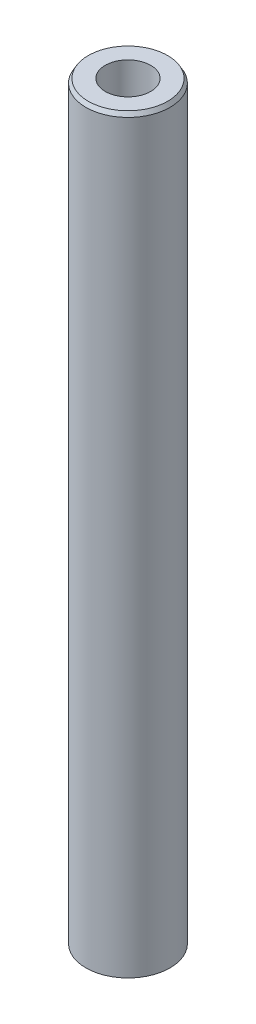
SolidWorks part; units mm, degrees
ref_plane "Front Plane" through (0, 0, 0) normal (0, 0, 1) x (1, 0, 0)
ref_plane "Top Plane" through (0, 0, 0) normal (0, 1, 0) x (1, 0, 0)
ref_plane "Right Plane" through (0, 0, 0) normal (1, 0, 0) x (0, 0, -1)
sketch "Sketch1" plane through (0, 0, 0) normal (0, 1, 0) x (1, 0, 0)
  circle A0 centre (0, 0) radius 20
  dimension "SHAFT_OD" = 40
extrude "Boss-Extrude1" add sketch "Sketch1" along normal blind 357.5993
sketch "Sketch2" plane through (0, 0, 0) normal (0, 1, 0) x (1, 0, 0)
  circle A0 centre (0, 0) radius 10.8052
  dimension "BORE_D" = 21.6103
extrude "Cut-Extrude1" cut sketch "Sketch2" along normal through all
chamfer "Chamfer1" distance 1.9557 angle 30 2 edges at (0, 357.5993, 20) (0, 0, 20) first distance on face at (0, 357.5993, 20) first distance on face at (0, 0, 10.8052)
